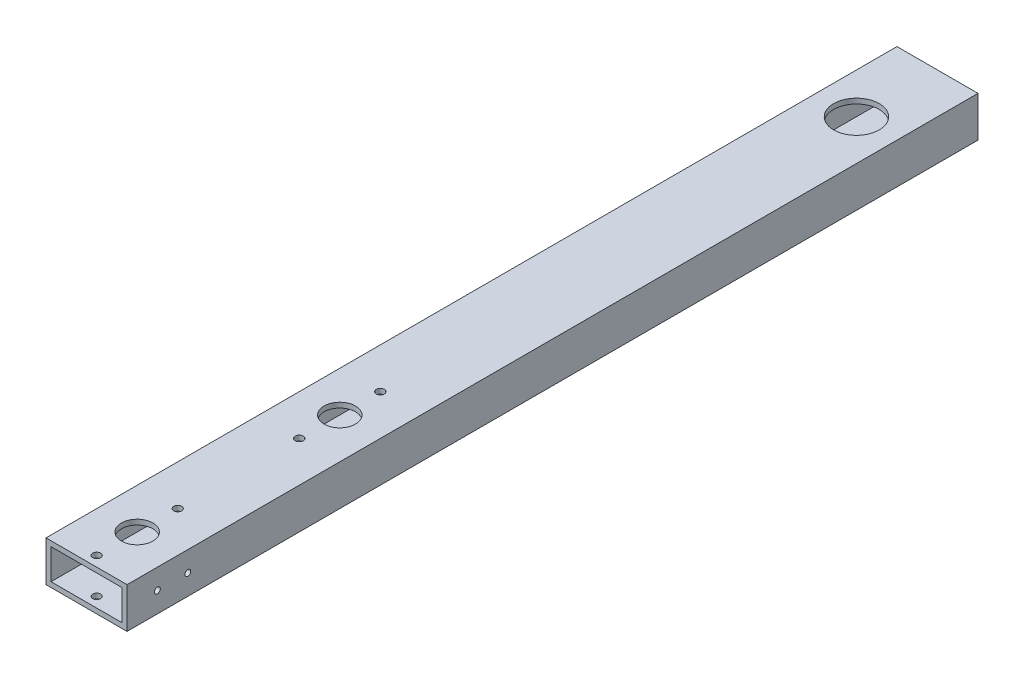
SolidWorks part; units mm, degrees
ref_plane "Front Plane" through (0, 0, 0) normal (0, 0, 1) x (1, 0, 0)
ref_plane "Top Plane" through (0, 0, 0) normal (0, 1, 0) x (1, 0, 0)
ref_plane "Right Plane" through (0, 0, 0) normal (1, 0, 0) x (0, 0, -1)
sketch "Sketch1" plane through (0, 0, 0) normal (0, 0, 1) x (1, 0, 0)
  line L1 (-25.4, -12.7) -> (25.4, -12.7)
  line L2 (-25.4, -12.7) -> (-25.4, 12.7)
  line L3 (-25.4, 12.7) -> (25.4, 12.7)
  line L4 (25.4, -12.7) -> (25.4, 12.7)
  line L5 (-25.4, -12.7) -> (25.4, 12.7) construction
  line L6 (-25.4, 12.7) -> (25.4, -12.7) construction
  point P0 (0, 0)
  dimension "D1" = 50.8
  dimension "D2" = 25.4
extrude "Boss-Extrude1" add sketch "Sketch1" along normal mid plane 533.4
sketch "Sketch2" plane through (0, 0, 266.7) normal (0, 0, 1) x (1, 0, 0)
  line L8 (22.225, -9.525) -> (22.225, 9.525)
  line L9 (22.225, 9.525) -> (-22.225, 9.525)
  line L10 (-22.225, 9.525) -> (-22.225, -9.525)
  line L11 (-22.225, -9.525) -> (22.225, -9.525)
  line L12 (22.225, -9.525) -> (22.225, 9.525)
  line L13 (22.225, 9.525) -> (-22.225, 9.525)
  line L14 (-22.225, 9.525) -> (-22.225, -9.525)
  line L15 (-22.225, -9.525) -> (22.225, -9.525)
  dimension "D1" = 3.175
extrude "Cut-Extrude1" cut sketch "Sketch2" against normal through all
sketch "Sketch5" plane through (0, 12.7, 0) normal (0, 1, 0) x (1, 0, 0)
  line L0 (25.4, -266.7) -> (25.4, 266.7) construction
  line L3 (0, 215.9) -> (0, -234.95) construction
  line L4 (22.225, -266.7) -> (-22.225, -266.7) construction
  circle A0 centre (0, -260.35) radius 2.4892
  circle A1 centre (0, -234.95) radius 9.8488
  circle A2 centre (0, -209.55) radius 2.4892
  circle A3 centre (0, 215.9) radius 14.2875
  point P14 (0, -266.7)
  dimension "D1" = 28.575
  dimension "D2" = 25.4
  dimension "D5" = 4.9784
  dimension "D6" = 19.6977
  dimension "D7" = 4.9784
  dimension "D8" = 25.4
  dimension "D3" = 450.85
  dimension "D9" = 25.4
  dimension "D10" = 6.35
extrude "Cut-Extrude2" cut sketch "Sketch5" against normal blind 508
sketch "Sketch7" plane through (0, 12.7, 0) normal (0, 1, 0) x (1, 0, 0)
  line L0 (-25.4, -266.7) -> (-25.4, 266.7) construction
  line L1 (0, -133.35) -> (0, -82.55) construction
  circle A0 centre (0, -107.95) radius 9.8488
  circle A1 centre (0, -234.95) radius 9.8488 construction
  circle A2 centre (0, -133.35) radius 2.5527
  circle A3 centre (0, -82.55) radius 2.5527
  dimension "D1" = 19.6977
  dimension "D2" = 127
  dimension "D4" = 5.1054
  dimension "D3" = 25.4
  dimension "D5" = 50.8
extrude "Cut-Extrude4" cut sketch "Sketch7" against normal through all
sketch "Sketch8" plane through (25.4, 0, 0) normal (1, 0, 0) x (0, 0, -1)
  line L0 (-266.7, -12.7) -> (-266.7, 12.7) construction
  circle A0 centre (-247.65, 0) radius 1.9812
  circle A1 centre (-228.6, 0) radius 1.9812
  dimension "D1" = 2
  dimension "D2" = 19.05
hole_wizard "#27 (0.144) Diameter Hole1" positions "Sketch10" profile "Sketch9" hole size "#27" standard "ANSI Inch" end condition through all
sketch "Sketch10" plane through (25.4, 0, 0) normal (1, 0, 0) x (0, 0, -1)
  point P0 (-247.65, 0)
  point P3 (-228.6, 0)
sketch "Sketch9" plane through (25.4, 0, 247.65) normal (0, 1, 0) x (0, 0, -1)
  line L0 (0, 0) -> (0, 50.8)
  line L1 (0, 50.8) -> (1.8288, 50.8)
  line L2 (1.8288, 50.8) -> (1.8288, 0)
  line L5 (1.8288, 0) -> (0, 0)
  line L11 (0, -6.35) -> (0, 107.95) construction
  dimension "Thru Hole Dia." = 3.6576
  dimension "Thru Hole Depth" = 50.8
